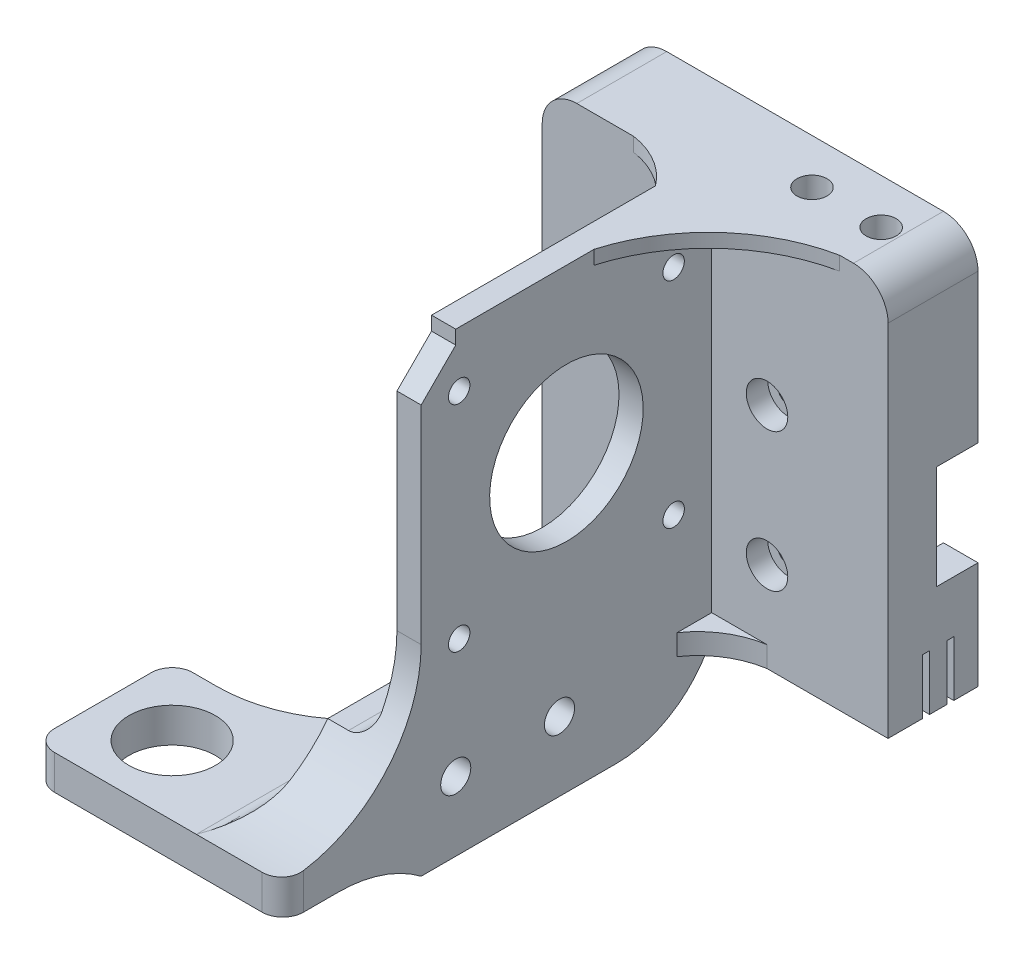
SolidWorks part; units mm, degrees
ref_plane "Alzado" through (0, 0, 0) normal (0, 0, 1) x (1, 0, 0)
ref_plane "Planta" through (0, 0, 0) normal (0, 1, 0) x (1, 0, 0)
ref_plane "Vista lateral" through (0, 0, 0) normal (1, 0, 0) x (0, 0, -1)
sketch "Croquis1" plane through (0, 0, 0) normal (0, 1, 0) x (1, 0, 0)
  line L1 (0, 0) -> (50, 0)
  line L2 (0, 0) -> (0, 13)
  line L3 (0, 13) -> (50, 13)
  line L4 (50, 0) -> (50, 13)
  dimension "D1" = 50
  dimension "D2" = 13
extrude "Saliente-Extruir1" add sketch "Croquis1" along normal blind 50
sketch "Croquis2" plane through (0, 0, 0) normal (0, -1, 0) x (1, 0, 0)
  line L0 (0, -13) -> (0, 0) construction
  line L1 (0, -5) -> (50, -5)
  line L2 (0, -5) -> (0, -7)
  line L3 (0, -7) -> (1, -7)
  line L4 (50, -5) -> (50, -6)
  line L6 (0, 0) -> (50, 0) construction
  line L7 (4, -7) -> (4, -6)
  line L9 (1, -7) -> (1, -6)
  line L10 (1, -6) -> (2, -6)
  line L11 (2, -7) -> (2, -6)
  line L12 (3, -6) -> (4, -6)
  line L13 (3, -7) -> (3, -6)
  line L14 (6, -7) -> (6, -6)
  line L15 (5, -6) -> (6, -6)
  line L16 (5, -7) -> (5, -6)
  line L17 (8, -7) -> (8, -6)
  line L18 (7, -6) -> (8, -6)
  line L19 (7, -7) -> (7, -6)
  line L20 (10, -7) -> (10, -6)
  line L21 (9, -6) -> (10, -6)
  line L22 (9, -7) -> (9, -6)
  line L23 (12, -7) -> (12, -6)
  line L24 (11, -6) -> (12, -6)
  line L25 (11, -7) -> (11, -6)
  line L26 (14, -7) -> (14, -6)
  line L27 (13, -6) -> (14, -6)
  line L28 (13, -7) -> (13, -6)
  line L29 (16, -7) -> (16, -6)
  line L30 (15, -6) -> (16, -6)
  line L31 (15, -7) -> (15, -6)
  line L32 (18, -7) -> (18, -6)
  line L33 (17, -6) -> (18, -6)
  line L34 (17, -7) -> (17, -6)
  line L35 (20, -7) -> (20, -6)
  line L36 (19, -6) -> (20, -6)
  line L37 (19, -7) -> (19, -6)
  line L38 (22, -7) -> (22, -6)
  line L39 (21, -6) -> (22, -6)
  line L40 (21, -7) -> (21, -6)
  line L41 (24, -7) -> (24, -6)
  line L42 (23, -6) -> (24, -6)
  line L43 (23, -7) -> (23, -6)
  line L44 (26, -7) -> (26, -6)
  line L45 (25, -6) -> (26, -6)
  line L46 (25, -7) -> (25, -6)
  line L47 (28, -7) -> (28, -6)
  line L48 (27, -6) -> (28, -6)
  line L49 (27, -7) -> (27, -6)
  line L50 (30, -7) -> (30, -6)
  line L51 (29, -6) -> (30, -6)
  line L52 (29, -7) -> (29, -6)
  line L53 (32, -7) -> (32, -6)
  line L54 (31, -6) -> (32, -6)
  line L55 (31, -7) -> (31, -6)
  line L56 (34, -7) -> (34, -6)
  line L57 (33, -6) -> (34, -6)
  line L58 (33, -7) -> (33, -6)
  line L59 (36, -7) -> (36, -6)
  line L60 (35, -6) -> (36, -6)
  line L61 (35, -7) -> (35, -6)
  line L62 (38, -7) -> (38, -6)
  line L63 (37, -6) -> (38, -6)
  line L64 (37, -7) -> (37, -6)
  line L65 (40, -7) -> (40, -6)
  line L66 (39, -6) -> (40, -6)
  line L67 (39, -7) -> (39, -6)
  line L68 (42, -7) -> (42, -6)
  line L69 (41, -6) -> (42, -6)
  line L70 (41, -7) -> (41, -6)
  line L71 (44, -7) -> (44, -6)
  line L72 (43, -6) -> (44, -6)
  line L73 (43, -7) -> (43, -6)
  line L74 (46, -7) -> (46, -6)
  line L75 (45, -6) -> (46, -6)
  line L76 (45, -7) -> (45, -6)
  line L77 (48, -7) -> (48, -6)
  line L78 (47, -6) -> (48, -6)
  line L79 (47, -7) -> (47, -6)
  line L81 (49, -6) -> (50, -6)
  line L82 (49, -7) -> (49, -6)
  line L83 (2, -7) -> (3, -7)
  line L84 (4, -7) -> (5, -7)
  line L85 (6, -7) -> (7, -7)
  line L86 (8, -7) -> (9, -7)
  line L87 (10, -7) -> (11, -7)
  line L88 (12, -7) -> (13, -7)
  line L89 (14, -7) -> (15, -7)
  line L90 (16, -7) -> (17, -7)
  line L91 (18, -7) -> (19, -7)
  line L92 (20, -7) -> (21, -7)
  line L93 (22, -7) -> (23, -7)
  line L94 (24, -7) -> (25, -7)
  line L95 (26, -7) -> (27, -7)
  line L96 (28, -7) -> (29, -7)
  line L97 (30, -7) -> (31, -7)
  line L98 (32, -7) -> (33, -7)
  line L99 (34, -7) -> (35, -7)
  line L100 (36, -7) -> (37, -7)
  line L101 (38, -7) -> (39, -7)
  line L102 (40, -7) -> (41, -7)
  line L103 (42, -7) -> (43, -7)
  line L104 (44, -7) -> (45, -7)
  line L105 (46, -7) -> (47, -7)
  line L106 (48, -7) -> (49, -7)
  line L107 (50, -7) -> (50, -6) [skipped]
  line L108 (0, -8.5) -> (50, -8.5)
  line L109 (0, -8.5) -> (0, -10.5)
  line L110 (0, -10.5) -> (1, -10.5)
  line L111 (50, -8.5) -> (50, -9.5)
  line L112 (4, -10.5) -> (4, -9.5)
  line L113 (1, -10.5) -> (1, -9.5)
  line L114 (1, -9.5) -> (2, -9.5)
  line L115 (2, -10.5) -> (2, -9.5)
  line L116 (3, -9.5) -> (4, -9.5)
  line L117 (3, -10.5) -> (3, -9.5)
  line L118 (6, -10.5) -> (6, -9.5)
  line L119 (5, -9.5) -> (6, -9.5)
  line L120 (5, -10.5) -> (5, -9.5)
  line L121 (8, -10.5) -> (8, -9.5)
  line L122 (7, -9.5) -> (8, -9.5)
  line L123 (7, -10.5) -> (7, -9.5)
  line L124 (10, -10.5) -> (10, -9.5)
  line L125 (9, -9.5) -> (10, -9.5)
  line L126 (9, -10.5) -> (9, -9.5)
  line L127 (12, -10.5) -> (12, -9.5)
  line L128 (11, -9.5) -> (12, -9.5)
  line L129 (11, -10.5) -> (11, -9.5)
  line L130 (14, -10.5) -> (14, -9.5)
  line L131 (13, -9.5) -> (14, -9.5)
  line L132 (13, -10.5) -> (13, -9.5)
  line L133 (16, -10.5) -> (16, -9.5)
  line L134 (15, -9.5) -> (16, -9.5)
  line L135 (15, -10.5) -> (15, -9.5)
  line L136 (18, -10.5) -> (18, -9.5)
  line L137 (17, -9.5) -> (18, -9.5)
  line L138 (17, -10.5) -> (17, -9.5)
  line L139 (20, -10.5) -> (20, -9.5)
  line L140 (19, -9.5) -> (20, -9.5)
  line L141 (19, -10.5) -> (19, -9.5)
  line L142 (22, -10.5) -> (22, -9.5)
  line L143 (21, -9.5) -> (22, -9.5)
  line L144 (21, -10.5) -> (21, -9.5)
  line L145 (24, -10.5) -> (24, -9.5)
  line L146 (23, -9.5) -> (24, -9.5)
  line L147 (23, -10.5) -> (23, -9.5)
  line L148 (26, -10.5) -> (26, -9.5)
  line L149 (25, -9.5) -> (26, -9.5)
  line L150 (25, -10.5) -> (25, -9.5)
  line L151 (28, -10.5) -> (28, -9.5)
  line L152 (27, -9.5) -> (28, -9.5)
  line L153 (27, -10.5) -> (27, -9.5)
  line L154 (30, -10.5) -> (30, -9.5)
  line L155 (29, -9.5) -> (30, -9.5)
  line L156 (29, -10.5) -> (29, -9.5)
  line L157 (32, -10.5) -> (32, -9.5)
  line L158 (31, -9.5) -> (32, -9.5)
  line L159 (31, -10.5) -> (31, -9.5)
  line L160 (34, -10.5) -> (34, -9.5)
  line L161 (33, -9.5) -> (34, -9.5)
  line L162 (33, -10.5) -> (33, -9.5)
  line L163 (36, -10.5) -> (36, -9.5)
  line L164 (35, -9.5) -> (36, -9.5)
  line L165 (35, -10.5) -> (35, -9.5)
  line L166 (38, -10.5) -> (38, -9.5)
  line L167 (37, -9.5) -> (38, -9.5)
  line L168 (37, -10.5) -> (37, -9.5)
  line L169 (40, -10.5) -> (40, -9.5)
  line L170 (39, -9.5) -> (40, -9.5)
  line L171 (39, -10.5) -> (39, -9.5)
  line L172 (42, -10.5) -> (42, -9.5)
  line L173 (41, -9.5) -> (42, -9.5)
  line L174 (41, -10.5) -> (41, -9.5)
  line L175 (44, -10.5) -> (44, -9.5)
  line L176 (43, -9.5) -> (44, -9.5)
  line L177 (43, -10.5) -> (43, -9.5)
  line L178 (46, -10.5) -> (46, -9.5)
  line L179 (45, -9.5) -> (46, -9.5)
  line L180 (45, -10.5) -> (45, -9.5)
  line L181 (48, -10.5) -> (48, -9.5)
  line L182 (47, -9.5) -> (48, -9.5)
  line L183 (47, -10.5) -> (47, -9.5)
  line L184 (49, -9.5) -> (50, -9.5)
  line L185 (49, -10.5) -> (49, -9.5)
  line L186 (2, -10.5) -> (3, -10.5)
  line L187 (4, -10.5) -> (5, -10.5)
  line L188 (6, -10.5) -> (7, -10.5)
  line L189 (8, -10.5) -> (9, -10.5)
  line L190 (10, -10.5) -> (11, -10.5)
  line L191 (12, -10.5) -> (13, -10.5)
  line L192 (14, -10.5) -> (15, -10.5)
  line L193 (16, -10.5) -> (17, -10.5)
  line L194 (18, -10.5) -> (19, -10.5)
  line L195 (20, -10.5) -> (21, -10.5)
  line L196 (22, -10.5) -> (23, -10.5)
  line L197 (24, -10.5) -> (25, -10.5)
  line L198 (26, -10.5) -> (27, -10.5)
  line L199 (28, -10.5) -> (29, -10.5)
  line L200 (30, -10.5) -> (31, -10.5)
  line L201 (32, -10.5) -> (33, -10.5)
  line L202 (34, -10.5) -> (35, -10.5)
  line L203 (36, -10.5) -> (37, -10.5)
  line L204 (38, -10.5) -> (39, -10.5)
  line L205 (40, -10.5) -> (41, -10.5)
  line L206 (42, -10.5) -> (43, -10.5)
  line L207 (44, -10.5) -> (45, -10.5)
  line L208 (46, -10.5) -> (47, -10.5)
  line L209 (48, -10.5) -> (49, -10.5)
  dimension "D1" = 5
  dimension "D2" = 2
  dimension "D3" = 1
  dimension "D4" = 1
  dimension "D5" = 1
  dimension "D7" = 1
  dimension "D9" = 3.5
  dimension "D6" = 25
  dimension "D8" = 2
extrude "Cortar-Extruir1" cut sketch "Croquis2" against normal blind 8
sketch "Croquis3" plane through (0, 0, 0) normal (0, 0, 1) x (1, 0, 0)
  line L0 (50, 50) -> (50, 0) construction
  line L2 (0, 0) -> (50, 0) construction
  circle A0 centre (17.5, 33) radius 1.55
  circle A1 centre (32.5, 33) radius 1.55
  circle A2 centre (17.5, 13) radius 1.55
  circle A3 centre (32.5, 13) radius 1.55
  dimension "D1" = 3.1
  dimension "D2" = 15
  dimension "D3" = 20
  dimension "D4" = 20
  dimension "D5" = 15
  dimension "D6" = 17.5
  dimension "D7" = 13
extrude "Cortar-Extruir2" cut sketch "Croquis3" against normal up to surface (13 mm away) up to face at (25, 25, -13)
sketch "Croquis6" plane through (0, 0, -13) normal (0, 0, -1) x (-1, 0, 0)
  line L0 (-50, 50) -> (-50, 0) construction
  line L1 (-45, 37) -> (-5, 37)
  line L2 (-45, 37) -> (-45, 30.5)
  line L3 (-45, 9) -> (-5, 9)
  line L4 (-5, 37) -> (-5, 30.5)
  line L5 (0, 50) -> (0, 0) construction
  line L6 (0, 30.5) -> (-5, 30.5)
  line L7 (0, 30.5) -> (0, 15.5)
  line L8 (0, 15.5) -> (-5, 15.5)
  line L9 (-50, 30.5) -> (-50, 15.5)
  line L10 (-45, 15.5) -> (-45, 9)
  line L11 (-45, 30.5) -> (-50, 30.5)
  line L12 (-45, 15.5) -> (-50, 15.5)
  line L13 (-5, 15.5) -> (-5, 9)
  circle A0 centre (-17.5, 13) radius 1.55 construction
  dimension "D1" = 40
  dimension "D2" = 28
  dimension "D3" = 5
  dimension "D4" = 4
  dimension "D5" = 15
  dimension "D6" = 6.5
extrude "Cortar-Extruir3" cut sketch "Croquis6" against normal blind 6
sketch "Croquis7" plane through (0, 0, 0) normal (0, 0, 1) x (1, 0, 0)
  line L1 (21, 55) -> (24.5, 55)
  line L2 (21, 55) -> (21, 8)
  line L3 (21, 8) -> (24.5, 8)
  line L4 (24.5, 55) -> (24.5, 8)
  circle A0 centre (32.5, 33) radius 1.55 construction
  dimension "D1" = 3.5
  dimension "D2" = 8
  dimension "D3" = 47
  dimension "D4" = 8
extrude "Saliente-Extruir2" add sketch "Croquis7" along normal blind 42
sketch "Croquis9" plane through (0, 0, 0) normal (0, 0, 1) x (1, 0, 0)
  circle A0 centre (17.5, 33) radius 3
  circle A1 centre (32.5, 33) radius 3
  circle A2 centre (32.5, 13) radius 3
  circle A3 centre (17.5, 13) radius 3
  dimension "D1" = 6
extrude "Cortar-Extruir5" cut sketch "Croquis9" against normal blind 3.1
sketch "Croquis8" plane through (21, 0, 0) normal (-1, 0, 0) x (0, 0, 1)
  line L0 (42, 55) -> (42, 8) construction
  line L1 (42, 55) -> (0, 55) construction
  circle A0 centre (21, 33.5) radius 11.1
  circle A2 centre (36.5, 49) radius 1.55
  circle A3 centre (36.5, 18) radius 1.55
  circle A4 centre (5.5, 49) radius 1.55
  circle A5 centre (5.5, 18) radius 1.55
  dimension "D1" = 22.2
  dimension "D3" = 21.5
  dimension "D4" = 3.1
  dimension "D6" = 3.1
  dimension "D7" = 31
  dimension "D2" = 21
  dimension "D5" = 31
  dimension "D8" = 31
  dimension "D9" = 15.5
  dimension "D10" = 15.5
extrude "Cortar-Extruir4" cut sketch "Croquis8" against normal up to surface (3.5 mm away) up to face at (24.5, 35.2, 16.8)
sketch "Croquis10" plane through (0, 50, 0) normal (0, 1, 0) x (1, 0, 0)
  line L6 (0, 13) -> (0, 0)
  line L7 (0, 0) -> (21, 0)
  line L8 (21, 0) -> (24.5, 0)
  line L9 (24.5, 0) -> (50, 0)
  line L10 (50, 0) -> (50, 13)
  line L11 (50, 13) -> (0, 13)
  line L12 (0, 13) -> (0, 0)
  line L13 (0, 0) -> (21, 0)
  line L14 (21, 0) -> (24.5, 0)
  line L15 (24.5, 0) -> (50, 0)
  line L16 (50, 0) -> (50, 13)
  line L17 (50, 13) -> (0, 13)
  dimension "D1" = 0
extrude "Saliente-Extruir3" add sketch "Croquis10" along normal blind 7
sketch "Croquis11" plane through (0, 57, 0) normal (0, 1, 0) x (1, 0, 0)
  line L0 (0, 0) -> (50, 0) construction
  line L1 (21, -42) -> (21, 0) construction
  line L2 (24.5, -42) -> (24.5, 0) construction
  line L3 (43, 0) -> (13.2138, 0)
  line L4 (24.5, -17) -> (21, -17)
  line L5 (21, -17) -> (21, -4.6215)
  line L6 (50, 0) -> (50, 13) construction
  line L7 (24.5, -42) -> (21, -42) construction
  arc A0 (13.2138, 0) -> (21, -4.6215) centre (11.4346, -11.8674) cw
  arc A1 (24.5, -17) -> (43, 0) centre (47.7502, -23.7355) cw
  dimension "D1" = 12
  dimension "D2" = 7
  dimension "D3" = 25
extrude "Saliente-Extruir4" add sketch "Croquis11" against normal up to surface (2 mm away) up to face at (22.75, 55, 21)
sketch "Croquis12" plane through (0, 8, 0) normal (0, -1, 0) x (1, 0, 0)
  line L4 (21, 0) -> (24.5, 0)
  line L5 (24.5, 0) -> (24.5, 42)
  line L6 (24.5, 42) -> (21, 42)
  line L7 (21, 42) -> (21, 0)
  line L8 (21, 0) -> (24.5, 0)
  line L9 (24.5, 0) -> (24.5, 42)
  line L10 (24.5, 42) -> (21, 42)
  line L11 (21, 42) -> (21, 0)
  dimension "D1" = 0
extrude "Saliente-Extruir5" add sketch "Croquis12" along normal blind 17
sketch "Croquis13" plane through (21, 0, 0) normal (-1, 0, 0) x (0, 0, 1)
  line L0 (42, 55) -> (42, -9) construction
  line L1 (0, -9) -> (42, -9)
  line L2 (0, -9) -> (0, 8)
  line L3 (0, 8) -> (42, 8)
  line L4 (42, -9) -> (42, 8)
  dimension "D1" = 17
extrude "Saliente-Extruir6" add sketch "Croquis13" along normal blind 6
sketch "Croquis14" plane through (24.5, 0, 0) normal (1, 0, 0) x (0, 0, -1)
  line L0 (-42, -9) -> (-42, 55) construction
  line L1 (0, -9) -> (-42, -9) construction
  circle A0 centre (-37, 1) radius 2.175
  circle A1 centre (-22, 1) radius 2.175
  dimension "D1" = 4.35
  dimension "D2" = 15
  dimension "D3" = 5
  dimension "D4" = 10
extrude "Cortar-Extruir6" cut sketch "Croquis14" against normal blind 4.5
sketch "Croquis15" plane through (0, 0, 42) normal (0, 0, 1) x (1, 0, 0)
  line L0 (24.5, 0) -> (24.5, 55) construction
  line L1 (24.5, 0) -> (-11.5, 0)
  line L2 (24.5, 0) -> (24.5, -5)
  line L3 (24.5, -5) -> (-11.5, -5)
  line L4 (-11.5, 0) -> (-11.5, -5)
  line L5 (24.5, -9) -> (15, -9) construction
  dimension "D1" = 5
  dimension "D2" = 4
  dimension "D3" = 36
extrude "Saliente-Extruir7" add sketch "Croquis15" along normal blind 20
sketch "Croquis16" plane through (0, 0, 0) normal (0, 1, 0) x (1, 0, 0)
  line L0 (-11.5, -52) -> (24.5, -52) construction
  line L1 (-11.5, -62) -> (-11.5, -42) construction
  line L2 (24.5, -62) -> (24.5, -42) construction
  circle A0 centre (-1.5, -52) radius 6.25
  dimension "D1" = 12.5
  dimension "D2" = 10
extrude "Cortar-Extruir7" cut sketch "Croquis16" against normal up to surface (5 mm away) up to face at (8.2, -5, 50)
fillet "Redondeo1" radius 20 1 edges at (19.75, -5, 42)
fillet "Redondeo2" radius 20 1 edges at (19.75, 0, 42)
fillet "Redondeo3" radius 20 1 edges at (15, -2.5, 42)
fillet "Redondeo4" radius 3 5 edges at (24.5, -2.5, 62) (-11.5, -2.5, 62) (-11.5, -2.5, 42) (15, 0, 42) (15, -5, 38)
fillet "Redondeo5" radius 15 1 edges at (19.75, -9, 0)
chamfer "Chaflán1" distance 5 angle 45 1 edges at (22.75, 55, 42)
fillet "Redondeo6" radius 3 1 edges at (21, 8, 23)
fillet "Redondeo7" radius 4 1 edges at (15, 4, 0)
sketch "Croquis17" plane through (0, 0, 0) normal (0, -1, 0) x (1, 0, 0)
  line L0 (24.5, 0) -> (50, 0) construction
  line L1 (32.5, 0) -> (24.5, 0)
  line L2 (24.5, 0) -> (11, 0) construction
  line L4 (24.5, 0) -> (24.5, 5)
  line L5 (24.5, 17) -> (24.5, 0) construction
  arc A1 (24.5, 5) -> (32.5, 0) centre (34.348, 11.8568) ccw
  dimension "D2" = 5
  dimension "D3" = 12
  dimension "D1" = 8
extrude "Saliente-Extruir8" add sketch "Croquis17" against normal blind 3
fillet "Redondeo8" radius 5 2 edges at (50, 57, -6.5) (0, 57, -6.5)
sketch "Croquis18" plane through (0, 57, 0) normal (0, 1, 0) x (1, 0, 0)
  line L0 (5, 6.5) -> (45, 6.5) construction
  line L1 (5, 13) -> (5, 0) construction
  line L2 (45, 0) -> (45, 13) construction
  circle A0 centre (32.5, 6.5) radius 2.175
  circle A1 centre (42.5, 6.5) radius 2.175
  dimension "D1" = 4.35
  dimension "D2" = 10
  dimension "D3" = 27.5
extrude "Cortar-Extruir8" cut sketch "Croquis18" against normal blind 4.5
sketch "Croquis20" plane through (0, 55, 0) normal (0, 1, 0) x (1, 0, 0)
  line L4 (21, -17) -> (21, -37)
  line L5 (21, -37) -> (24.5, -37)
  line L6 (24.5, -37) -> (24.5, -17)
  line L7 (24.5, -17) -> (21, -17)
  line L8 (21, -17) -> (21, -37)
  line L9 (21, -37) -> (24.5, -37)
  line L10 (24.5, -37) -> (24.5, -17)
  line L11 (24.5, -17) -> (21, -17)
  dimension "D1" = 0
extrude "Saliente-Extruir9" add sketch "Croquis20" along normal up to surface (2 mm away) up to face at (32.5, 57, -4.325)
